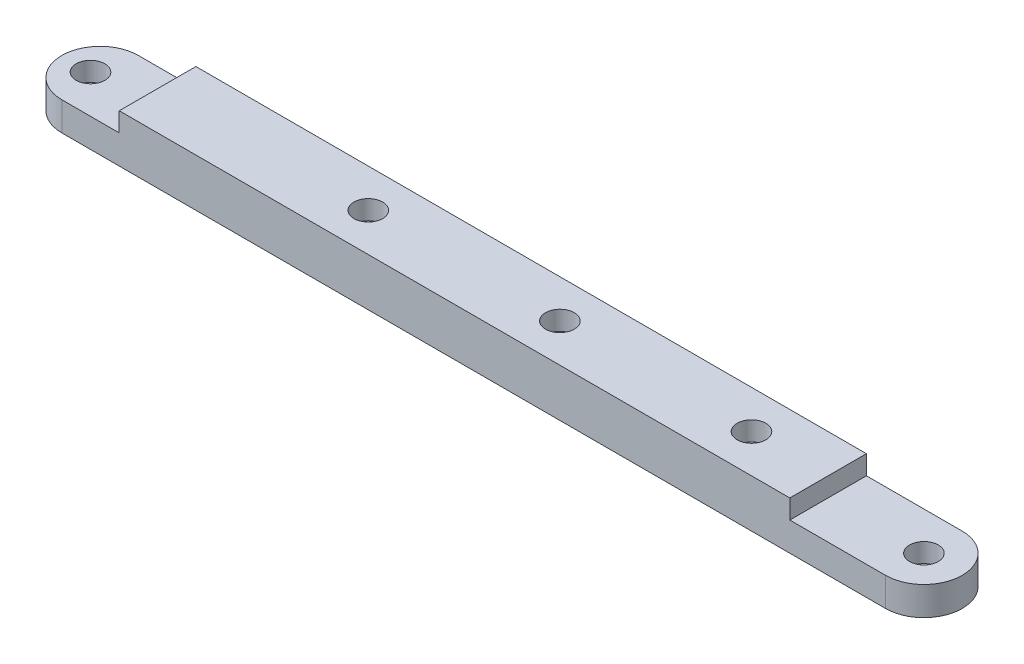
SolidWorks part; units mm, degrees
ref_plane "Front Plane" through (0, 0, 0) normal (0, 0, 1) x (1, 0, 0)
ref_plane "Top Plane" through (0, 0, 0) normal (0, 1, 0) x (1, 0, 0)
ref_plane "Right Plane" through (0, 0, 0) normal (1, 0, 0) x (0, 0, -1)
sketch "Sketch1" plane through (0, 0, 0) normal (0, 1, 0) x (1, 0, 0)
  line L0 (-25, -4) -> (65, -4)
  line L1 (65, 4) -> (-25, 4)
  line L2 (-25, 4) -> (-25, -4)
  arc A0 (65, -4) -> (65, 4) centre (65, 0) ccw
  dimension "D3" = 4
  dimension "D1" = 90
  dimension "D2" = 4
extrude "Boss-Extrude2" add sketch "Sketch1" along normal blind 3
sketch "Sketch3" plane through (0, 3, 0) normal (0, 1, 0) x (1, 0, 0)
  line L0 (-25, -4) -> (65, -4) construction
  line L1 (-25, 4) -> (55, 4)
  line L2 (-25, 4) -> (-25, -4)
  line L3 (-25, -4) -> (55, -4)
  line L4 (55, 4) -> (55, -4)
  dimension "D1" = 80
extrude "Boss-Extrude3" add sketch "Sketch3" along normal blind 2
sketch "Sketch4" plane through (0, 3, 0) normal (0, 1, 0) x (1, 0, 0)
  circle A0 centre (65, 0) radius 1.5
  dimension "D1" = 3
sketch "Sketch12" plane through (0, 5, 0) normal (0, 1, 0) x (1, 0, 0)
  line L0 (55, -4) -> (55, 4) construction
  circle A0 centre (47, 0) radius 1.5
  circle A1 centre (27, 0) radius 1.5
  circle A2 centre (7, 0) radius 1.5
  dimension "D1" = 3
  dimension "D2" = 8
  dimension "D3" = 3
extrude "Cut-Extrude5" cut sketch "Sketch4" against normal blind 2
extrude "Cut-Extrude6" cut sketch "Sketch12" against normal blind 2
sketch "Sketch16" plane through (0, 5, 0) normal (0, 1, 0) x (1, 0, 0)
  line L0 (-25, -4) -> (55, -4) construction
  line L1 (-25, 4) -> (-15, 4)
  line L2 (-25, 4) -> (-25, -4)
  line L3 (-25, -4) -> (-15, -4)
  line L4 (-15, 4) -> (-15, -4)
  dimension "D1" = 10
extrude "Cut-Extrude7" cut sketch "Sketch16" against normal blind 2
sketch "Sketch17" plane through (0, 3, 0) normal (0, 1, 0) x (1, 0, 0)
  line L0 (-25, 0) -> (-15, 0) construction
  line L1 (-25, 4) -> (-25, -4) construction
  line L2 (-15, -4) -> (-15, 4) construction
  circle A0 centre (-22, 0) radius 1.5
  dimension "D1" = 3
  dimension "D2" = 3
extrude "Cut-Extrude8" cut sketch "Sketch17" against normal blind 2
fillet "Fillet1" radius 4 2 edges at (-25, 1.5, -4) (-25, 1.5, 4)
